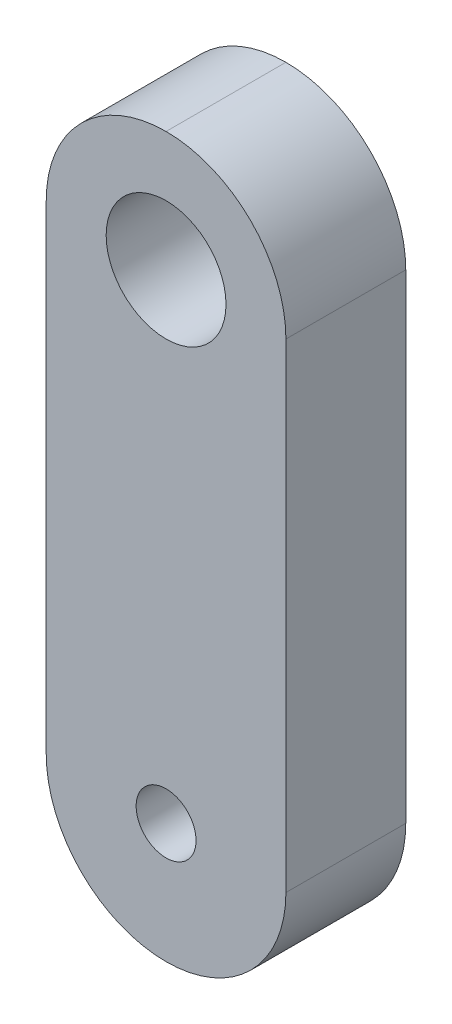
SolidWorks part; units mm, degrees
ref_plane "Plan de face" through (0, 0, 0) normal (0, 0, 1) x (1, 0, 0)
ref_plane "Plan de dessus" through (0, 0, 0) normal (0, 1, 0) x (1, 0, 0)
ref_plane "Plan de droite" through (0, 0, 0) normal (1, 0, 0) x (0, 0, -1)
sketch "Esquisse1" plane through (0, 0, 0) normal (0, 0, 1) x (1, 0, 0)
  line L1 (0, 0) -> (20, 0)
  line L2 (0, 0) -> (0, 60)
  line L3 (0, 60) -> (20, 60)
  line L4 (20, 0) -> (20, 60)
  dimension "D1" = 20
  dimension "D2" = 60
extrude "Boss.-Extru.1" add sketch "Esquisse1" along normal blind 10
sketch "Esquisse2" plane through (0, 0, 10) normal (0, 0, 1) x (1, 0, 0)
  line L0 (10, 60) -> (10, 50) construction
  line L1 (20, 60) -> (0, 60) construction
  line L2 (10, 50) -> (0, 50) construction
  line L3 (0, 60) -> (0, 0) construction
  line L4 (10, 0) -> (10, 10) construction
  line L5 (0, 0) -> (20, 0) construction
  line L6 (10, 10) -> (0, 10) construction
  circle A0 centre (10, 50) radius 5
  circle A1 centre (10, 10) radius 2.5
  dimension "D1" = 10
  dimension "D2" = 5
extrude "Enlèv. mat.-Extru.1" cut sketch "Esquisse2" against normal through all both and the other way through all
fillet "Congé1" radius 10 4 edges at (0, 0, 5) (20, 0, 5) (0, 60, 5) (20, 60, 5)
